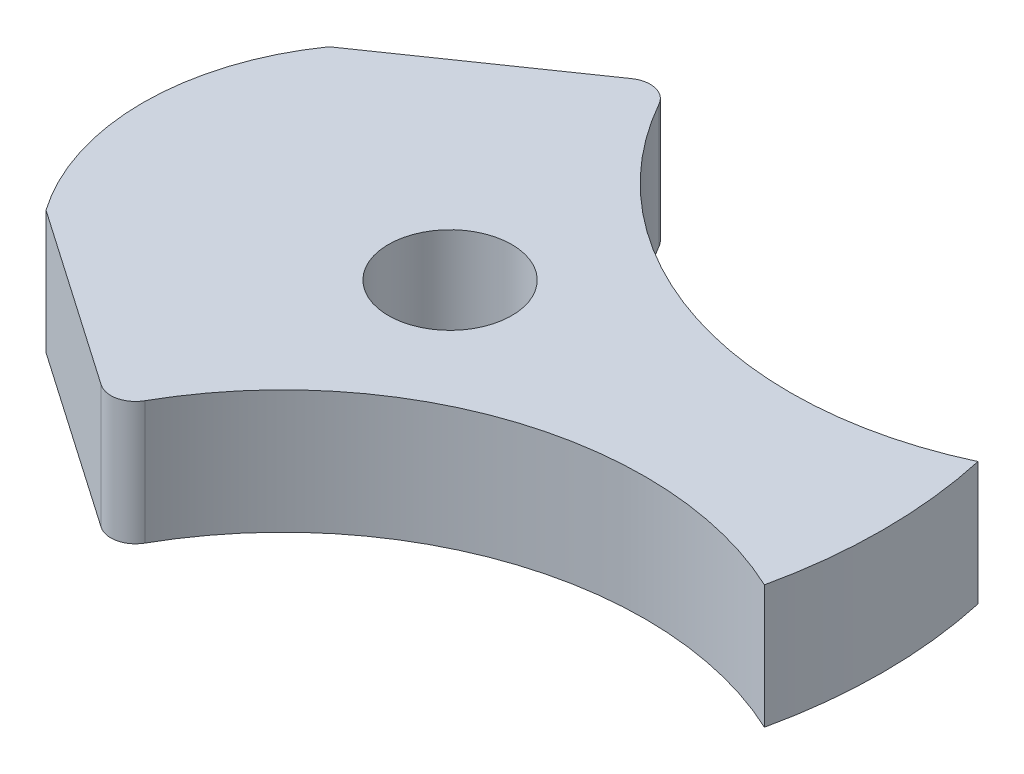
SolidWorks part; units mm, degrees
material "AISI Type A2 Tool Steel"
ref_plane "Front Plane" through (0, 0, 0) normal (0, 0, 1) x (1, 0, 0)
ref_plane "Top Plane" through (0, 0, 0) normal (0, 1, 0) x (1, 0, 0)
ref_plane "Right Plane" through (0, 0, 0) normal (1, 0, 0) x (0, 0, -1)
other "Center of Mass"
sketch "Sketch1" plane through (0, 0, 0) normal (0, 1, 0) x (1, 0, 0)
  line L0 (0, 0) -> (-50000, 0) construction
  line L1 (-20.8065, 14.5688) -> (-20.8065, 0) construction
  line L2 (-20.8065, -14.5688) -> (-20.8065, 0) construction
  line L3 (49.5958, 10.9951) -> (49.5958, 0) construction
  line L4 (49.5958, -10.9951) -> (49.5958, 0) construction
  line L5 (0, 0) -> (0, 50000) construction
  line L6 (-20.8065, 14.5688) -> (0, 28.9594)
  line L7 (-20.8065, -14.5688) -> (0, -28.9594)
  line L8 (-20.8065, 14.5688) -> (0, 14.5688) construction
  line L9 (-20.8065, -14.5688) -> (0, -14.5688) construction
  arc A0 (-20.8065, 14.5688) -> (-20.8065, -14.5688) centre (0, 0) ccw
  arc A1 (49.5958, 10.9951) -> (49.5958, -10.9951) centre (0, 0) cw
  arc A2 (49.5958, 10.9951) -> (0, 28.9594) centre (33.7801, 44.7752) cw
  arc A3 (0, -28.9594) -> (49.5958, -10.9951) centre (33.7801, -44.7752) cw
  dimension "D1" = 25.4
  dimension "D2" = 25
  dimension "D4" = 70
  dimension "D3" = 50.8
  dimension "D6" = 37.2992
  dimension "D5" = 28.9594
extrude "Boss-Extrude1" add sketch "Sketch1" along normal blind 12.7
sketch "Sketch3" plane through (0, 0, 0) normal (0, -1, 0) x (1, 0, 0)
  circle A0 centre (6.2319, 0) radius 6.35
fillet "Fillet3" radius 2.54 1 edges at (0, 6.35, -28.9594)
fillet "Fillet4" radius 2.54 1 edges at (0, 6.35, 28.9594)
extrude "Cut-Extrude2" cut sketch "Sketch3" against normal through all contours A0
sketch "Sketch7" plane through (0, 12.7, 0) normal (0, 1, 0) x (1, 0, 0)
  line L0 (6.2319, 0) -> (50.8, 0) construction
  arc A0 (49.5958, -10.9951) -> (49.5958, 10.9951) centre (0, 0) ccw construction
sketch "Sketch9" plane through (0, 12.7, 0) normal (0, 1, 0) x (1, 0, 0)
